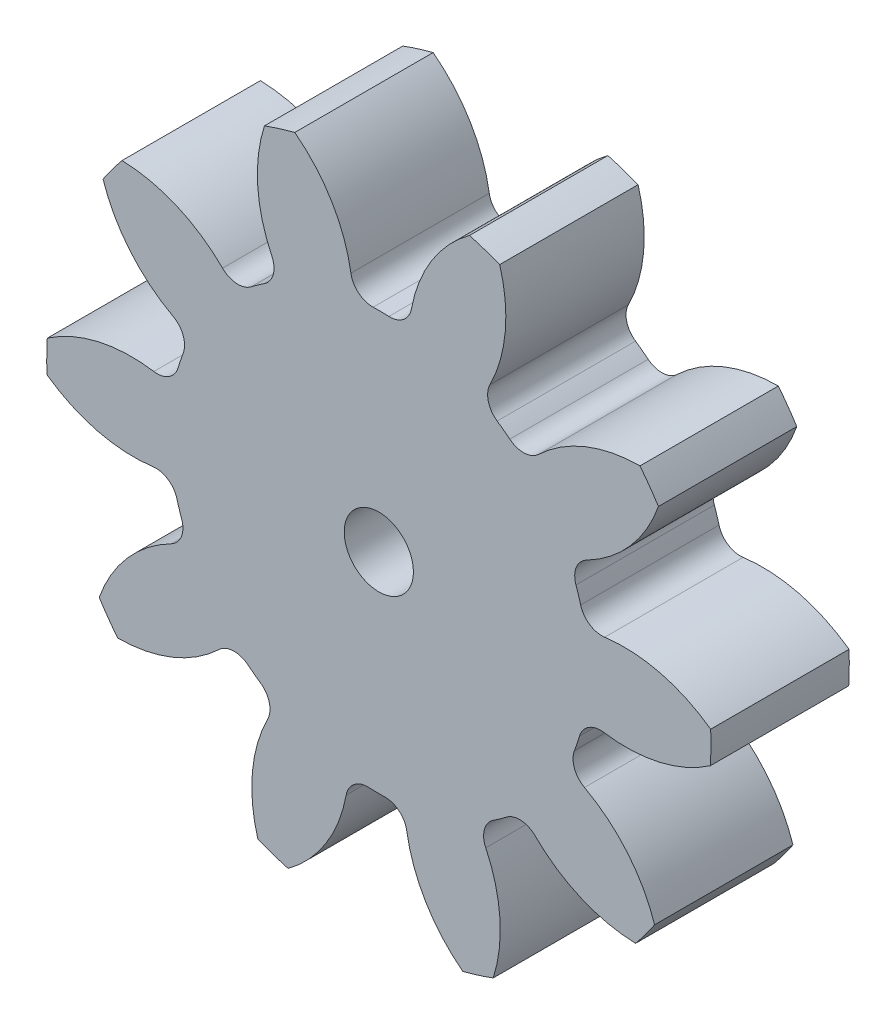
SolidWorks part; units mm, degrees
ref_plane "Front" through (0, 0, 0) normal (0, 0, 1) x (1, 0, 0)
ref_plane "Top" through (0, 0, 0) normal (0, 1, 0) x (1, 0, 0)
ref_plane "Right" through (0, 0, 0) normal (1, 0, 0) x (0, 0, -1)
sketch "Sketch3" plane through (0, 0, 0) normal (0, 0, 1) x (1, 0, 0)
  circle A0 centre (0, 0) radius 15.24
  dimension "od" = 30.48
extrude "gearBody" add sketch "Sketch3" along normal blind 6.35
sketch "Sketch2" plane through (0, 0, 0) normal (0, 0, 1) x (1, 0, 0)
  line L0 (0, 0) -> (11.3595, 4.7053) construction
  line L1 (12.8367, -12.0857) -> (0, 0) construction
  line L2 (0, 0) -> (36.3143, 0) construction
  line L3 (12.544, -1.9847) -> (11.1917, -6.003) construction
  line L5 (11.8678, -3.9939) -> (0, 0) construction
  line L7 (0, 0) -> (12.2955, 0) construction
  arc A0 (12.1241, -2.0456) -> (10.8941, -5.7007) centre (0, 0) ccw construction
  arc A1 (15.214, -0.8896) -> (12.6563, -8.4897) centre (0, 0) ccw construction
  arc A2 (12.544, -1.9847) -> (11.1917, -6.003) centre (0, 0) ccw construction
  arc A3 (8.9781, -3.4023) -> (9.2084, -2.718) centre (0, 0) ccw
  arc A4 (12.8367, -12.0857) -> (9.4391, -4.6417) centre (6.2035, -10.6158) ccw
  arc A5 (12.8367, -12.0857) -> (17.5318, 1.8658) centre (0, 0) ccw
  arc A6 (17.5318, 1.8658) -> (10.3249, -2.0095) centre (11.3595, 4.7053) cw
  arc A7 (9.2084, -2.718) -> (10.3249, -2.0095) centre (10.1719, -3.0024) cw
  arc A8 (9.4391, -4.6417) -> (8.9781, -3.4023) centre (9.9175, -3.7583) cw
  point P6 (17.5318, 1.8658)
  point P22 (12.8367, -12.0857)
  dimension "baseDia" = 24.591
  dimension "od" = 30.48
  dimension "pd" = 25.4
  dimension "rd" = 19.2024
  dimension "rFillet" = 1.0046
  dimension "pointX" = 17.5318
  dimension "pointY" = 1.8658
  dimension "CTT" = 4.0183
  dimension "flankCenterAngle" = 22.5
extrude "toothCut" cut sketch "Sketch2" along normal through all
pattern_circular "CirPattern1" count 10 over 360 about axis through (0, 0, 6.35) along (0, 0, -1) of "toothCut"
ref_axis "toothSpace" through (0, 0, 0) along (0.9478, -0.319, 0)
ref_axis "Axis2" through (12.235, -9.0864, 0) along (-0.8028, 0.5962, 0)
sketch "hub1Dia" plane through (0, 0, 0) normal (0, 0, -1) x (-1, 0, 0)
  circle A0 centre (0, 0) radius 12.7
  dimension "hub1Dia" = 25.4
sketch "hub2Dia" plane through (0, 0, 6.35) normal (0, 0, 1) x (1, 0, 0)
  circle A0 centre (0, 0) radius 12.7
  dimension "hub2dia" = 25.4
sketch "boreDia" plane through (0, 0, 0) normal (0, 0, 1) x (1, 0, 0)
  circle A0 centre (0, 0) radius 1.5875
  dimension "boreDia" = 3.175
extrude "bore" cut sketch "boreDia" against normal mid plane 25400
sketch "kwy1sketch" plane through (0, 0, 0) normal (0, 0, 1) x (1, 0, 0)
  line L0 (-4.3738, 2.5866) -> (0, 0) construction
  line L1 (31.0606, -3.6142) -> (18.131, -25.4772)
  line L2 (18.131, -25.4772) -> (-9.1976, -9.3153)
  line L3 (31.0606, -3.6142) -> (3.7319, 12.5477)
  line L4 (-9.1976, -9.3153) -> (0, 0)
  line L5 (0, 0) -> (3.7319, 12.5477)
  line L6 (0, 0) -> (9.0997, -3.0623) construction
  line L7 (24.5958, -14.5457) -> (0, 0) construction
  arc A7 (8.9781, -3.4023) -> (9.2084, -2.718) centre (0, 0) ccw construction
  point P9 (24.5958, -14.5457)
  point P13 (-0.7296, 0.4315)
  dimension "kwy1width" = 25.4
  dimension "kwy1depth" = 28.575
  dimension "kwy1angle" = 12
  dimension "kwy1Depth2" = 31.75
sketch "kwy2sketch" plane through (0, 0, 0) normal (0, 0, 1) x (1, 0, 0)
  line L0 (9.0997, -3.0623) -> (0, 0) construction
  line L1 (0, 0) -> (-3.4011, -0.8733) construction
  line L2 (24.5188, 19.4075) -> (30.8357, -5.1945)
  line L3 (30.8357, -5.1945) -> (0.0832, -13.0906)
  line L4 (24.5188, 19.4075) -> (-6.2337, 11.5114)
  line L5 (0.0832, -13.0906) -> (0, 0)
  line L6 (0, 0) -> (-6.2337, 11.5114)
  arc A2 (8.9781, -3.4023) -> (9.2084, -2.718) centre (0, 0) ccw construction
  point P10 (27.6772, 7.1065)
  dimension "kwy2angle" = 33
  dimension "kwy2Width" = 25.4
  dimension "kwy2depth" = 28.575
  dimension "kwy2Depth2" = 31.75
sketch "kwy3sketch" plane through (0, 0, 0) normal (0, 0, 1) x (1, 0, 0)
  line L0 (9.0997, -3.0623) -> (0, 0) construction
  line L1 (0, 0) -> (-1.2931, -2.1866) construction
  line L2 (3.6142, 31.0606) -> (25.4772, 18.131)
  line L3 (25.4772, 18.131) -> (9.3153, -9.1976)
  line L4 (3.6142, 31.0606) -> (-12.5477, 3.7319)
  line L5 (9.3153, -9.1976) -> (0, 0)
  line L6 (-12.5477, 3.7319) -> (0, 0)
  point P10 (14.5457, 24.5958)
  dimension "kwy3angle" = 78
  dimension "kwy3depth" = 28.575
  dimension "kwy3width" = 25.4
  dimension "kwy3Depth2" = 31.75
sketch "kwy4sketch" plane through (0, 0, 0) normal (0, 0, 1) x (1, 0, 0)
  line L0 (9.0997, -3.0623) -> (0, 0) construction
  line L1 (0, 0) -> (0.494, -1.9239) construction
  line L2 (5.1945, 30.8357) -> (-19.4075, 24.5188)
  line L3 (-19.4075, 24.5188) -> (-11.5114, -6.2337)
  line L4 (-11.5114, -6.2337) -> (0, 0)
  line L5 (13.0906, 0.0832) -> (0, 0)
  line L6 (5.1945, 30.8357) -> (13.0906, 0.0832)
  point P15 (-7.1065, 27.6772)
  dimension "kwy4angle" = 123
  dimension "kwy4depth" = 28.575
  dimension "kwy4width" = 25.4
  dimension "kwy4Depth2" = 31.75
sketch "kwy5sketch" plane through (0, 0, 0) normal (0, 0, 1) x (1, 0, 0)
  line L0 (9.0997, -3.0623) -> (0, 0) construction
  line L1 (0, 0) -> (1.4683, -0.8684) construction
  line L2 (-18.131, 25.4772) -> (-31.0606, 3.6142)
  line L3 (-31.0606, 3.6142) -> (-3.7319, -12.5477)
  line L4 (-18.131, 25.4772) -> (9.1976, 9.3153)
  line L5 (-3.7319, -12.5477) -> (0, 0)
  line L6 (9.1976, 9.3153) -> (0, 0)
  point P10 (-24.5958, 14.5457)
  dimension "kwy5width" = 25.4
  dimension "kwy5depth" = 28.575
  dimension "kwy5angle" = 168
  dimension "kwy5Depth2" = 31.75
sketch "kwy6sketch" plane through (0, 0, 0) normal (0, 0, 1) x (1, 0, 0)
  line L0 (9.0997, -3.0623) -> (0, 0) construction
  line L1 (0, 0) -> (1.651, 0.4239) construction
  line L2 (-30.8357, 5.1945) -> (-24.5188, -19.4075)
  line L3 (-24.5188, -19.4075) -> (6.2337, -11.5114)
  line L4 (-30.8357, 5.1945) -> (-0.0832, 13.0906)
  line L5 (6.2337, -11.5114) -> (0, 0)
  line L6 (-0.0832, 13.0906) -> (0, 0)
  point P10 (-27.6772, -7.1065)
  dimension "kwy6angle" = 213
  dimension "kwy6width" = 25.4
  dimension "kwy6depth" = 28.575
  dimension "kwy6Depth2" = 31.75
sketch "kwy7sketch" plane through (0, 0, 0) normal (0, 0, 1) x (1, 0, 0)
  line L0 (9.0997, -3.0623) -> (0, 0) construction
  line L1 (0, 0) -> (0.9721, 1.6437) construction
  line L2 (-25.4772, -18.131) -> (-3.6142, -31.0606)
  line L3 (-25.4772, -18.131) -> (-9.3153, 9.1976)
  line L4 (-3.6142, -31.0606) -> (12.5477, -3.7319)
  line L5 (-9.3153, 9.1976) -> (0, 0)
  line L6 (12.5477, -3.7319) -> (0, 0)
  point P10 (-14.5457, -24.5958)
  dimension "kwy7angle" = 78
  dimension "kwy7width" = 25.4
  dimension "kwy7depth" = 28.575
  dimension "kwy7angle1" = 258
  dimension "kwy7Depth2" = 31.75
sketch "kwy8sketch" plane through (0, 0, 0) normal (0, 0, 1) x (1, 0, 0)
  line L0 (9.0997, -3.0623) -> (0, 0) construction
  line L1 (0, 0) -> (-0.4219, 1.6433) construction
  line L2 (-5.1945, -30.8357) -> (19.4075, -24.5188)
  line L3 (19.4075, -24.5188) -> (11.5114, 6.2337)
  line L4 (-5.1945, -30.8357) -> (-13.0906, -0.0832)
  line L5 (11.5114, 6.2337) -> (0, 0)
  line L6 (-13.0906, -0.0832) -> (0, 0)
  point P10 (7.1065, -27.6772)
  dimension "kwy8angle" = 303
  dimension "kwy8width" = 25.4
  dimension "kwy8depth" = 28.575
  dimension "kwy8Depth2" = 31.75
sketch "centerLine" plane through (0, 0, 0) normal (0, 1, 0) x (1, 0, 0)
  line L0 (0, 36.4807) -> (0, -59.6309) construction
ref_plane "CB1plane" through (0, 0, 0) normal (0, 0, -1) x (-1, 0, 0)
sketch "CB1diameter" plane through (0, 0, 0) normal (0, 0, -1) x (-1, 0, 0)
  circle A0 centre (0, 0) radius 12.7
  dimension "CB1diameter" = 25.4
ref_plane "CB2plane" through (0, 0, 6.35) normal (0, 0, 1) x (1, 0, 0)
sketch "CB2diameter" plane through (0, 0, 6.35) normal (0, 0, 1) x (1, 0, 0)
  circle A0 centre (0, 0) radius 12.7
  dimension "CB2diameter" = 25.4
ref_axis "Axis1" through (0, 0, 50) along (0, 0, -1)
sketch3d "3DSketch1" plane through (0, 0, 0) normal (0, 0, 1) x (1, 0, 0)
